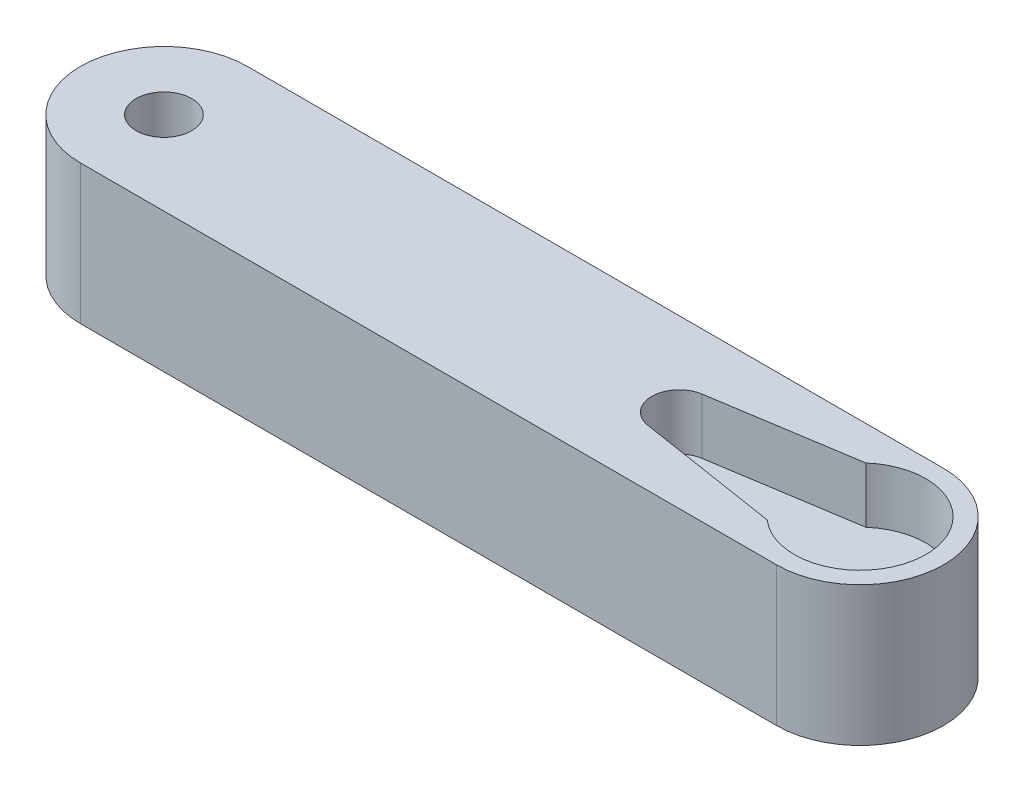
SolidWorks part; units mm, degrees
ref_plane "Front Plane" through (0, 0, 0) normal (0, 0, 1) x (1, 0, 0)
ref_plane "Top Plane" through (0, 0, 0) normal (0, 1, 0) x (1, 0, 0)
ref_plane "Right Plane" through (0, 0, 0) normal (1, 0, 0) x (0, 0, -1)
sketch "Sketch3" plane through (0, 0, 0) normal (0, 1, 0) x (1, 0, 0)
  line L0 (-31.75, 0) -> (31.75, 0) construction
  line L1 (-6.985, 0) -> (6.985, 0) construction
  line L2 (-31.75, 7.62) -> (31.75, 7.62)
  line L3 (-31.75, -7.62) -> (31.75, -7.62)
  arc A0 (-31.75, 7.62) -> (-31.75, -7.62) centre (-31.75, 0) ccw
  arc A1 (31.75, -7.62) -> (31.75, 7.62) centre (31.75, 0) ccw
  point P5 (0, 0)
  dimension "D2" = 7.62
  dimension "D1" = 63.5
  dimension "D3" = 31.75
extrude "Boss-Extrude1" add sketch "Sketch3" along normal blind 12.7
sketch "Sketch4" plane through (0, 12.7, 0) normal (0, 1, 0) x (1, 0, 0)
  circle A0 centre (-31.75, 0) radius 2.54
  dimension "D1" = 5.08
extrude "Cut-Extrude3" cut sketch "Sketch4" against normal through all
sketch "Sketch5" plane through (0, 12.7, 0) normal (0, 1, 0) x (1, 0, 0)
  line L0 (14.8619, -2.4697) -> (27.7814, -4.5)
  line L1 (27.7814, 4.5) -> (14.8619, 2.4697)
  arc A0 (14.8619, 2.4697) -> (14.8619, -2.4697) centre (15.25, 0) ccw
  arc A1 (27.7814, -4.5) -> (27.7814, 4.5) centre (31.75, 0) ccw
  dimension "D1" = 63.5
extrude "Cut-Extrude4" cut sketch "Sketch5" against normal blind 5.08
equation "\"TibiaLength\"= 5in"
equation "\"TibiaRadius\"= 0.3in"
equation "\"TibiaDistFromCentre\"= \"TibiaLength\" / 2"
equation "\"TibiaThickness\"= 0.5in"
equation "\"HoleRadius\"= 0.2in"
equation "\"D1@Sketch3\" = \"TibiaLength\" * 0.5"
equation "\"D2@Sketch3\"= \"TibiaRadius\""
equation "\"D3@Sketch3\"=\"TibiaDistFromCentre\"/2"
equation "\"D1@Boss-Extrude1\"= \"TibiaThickness\""
equation "\"D1@Sketch4\"= \"HoleRadius\""
equation "\"D1@Sketch5\"=\"TibiaLength\"/2"
